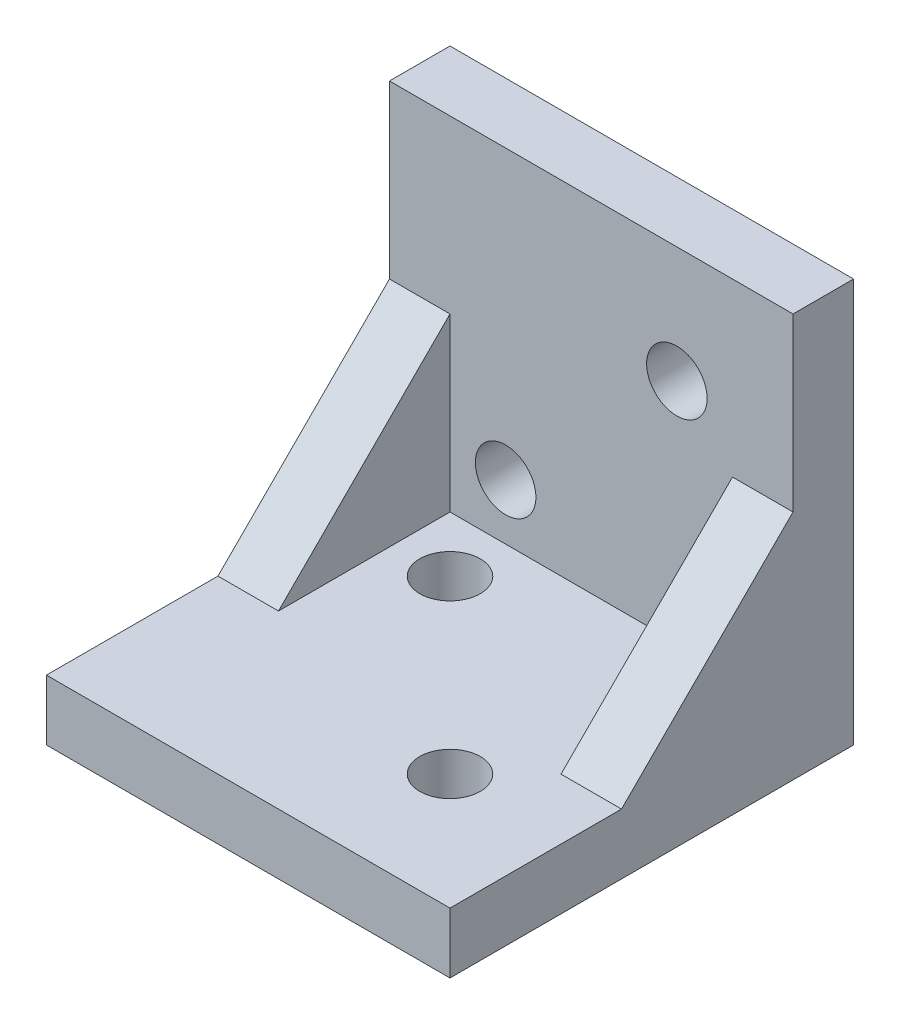
SolidWorks part; units mm, degrees
ref_plane "Front Plane" through (0, 0, 0) normal (0, 0, 1) x (1, 0, 0)
ref_plane "Top Plane" through (0, 0, 0) normal (0, 1, 0) x (1, 0, 0)
ref_plane "Right Plane" through (0, 0, 0) normal (1, 0, 0) x (0, 0, -1)
sketch "Sketch1" plane through (0, 0, 0) normal (0, 1, 0) x (1, 0, 0)
  line L0 (0, 0) -> (-10, 10) construction
  line L1 (-10, -10) -> (10, -10)
  line L2 (-10, -10) -> (-10, 10)
  line L3 (-10, 10) -> (10, 10)
  line L4 (10, -10) -> (10, 10)
  line L5 (-10, -10) -> (10, 10) construction
  line L7 (0, 0) -> (10, -10) construction
  circle A0 centre (-4.2426, 4.2426) radius 1.5
  circle A2 centre (4.2426, -4.2426) radius 1.5
  point P0 (0, 0)
  point P9 (-5, 5)
  point P10 (4.1299, -3.2213)
  point P12 (0, 0)
  point P13 (0, 0)
  point P14 (0, 0)
  point P15 (0, 0)
  point P16 (-23.6436, 6.8969)
  point P17 (-4.4087, 4.4087)
  dimension "D3" = 3
  dimension "D4" = 3
  dimension "D1" = 20
  dimension "D2" = 20
  dimension "D5" = 6
extrude "Boss-Extrude1" add sketch "Sketch1" along normal blind 3
sketch "Sketch2" plane through (0, 3, 0) normal (0, 1, 0) x (1, 0, 0)
  line L0 (10, -10) -> (10, 10) construction
  line L1 (-10, 10) -> (10, 10)
  line L2 (-10, 10) -> (-10, 7)
  line L3 (-10, 7) -> (10, 7)
  line L4 (10, 10) -> (10, 7)
  dimension "D1" = 3
extrude "Boss-Extrude2" add sketch "Sketch2" along normal blind 17
sketch "Sketch3" plane through (0, 0, -10) normal (0, 0, -1) x (-1, 0, 0)
  line L1 (-10, 20) -> (-10, 0) construction
  line L2 (10, 20) -> (10, 0) construction
  line L4 (-10, 20) -> (0, 10) construction
  line L5 (0, 11) -> (0, -11) construction
  line L6 (0, 10) -> (10, 0) construction
  line L7 (-10, 0) -> (10, 20) construction
  line L10 (11, 0) -> (-11, 0) construction
  circle A0 centre (-4.2426, 14.2426) radius 1.5
  circle A1 centre (4.2426, 5.7574) radius 1.5
  point P6 (-10, 0)
  point P13 (0, 0)
  point P19 (-0.8673, 14.6461)
  point P21 (10, 0)
  point P24 (-3.2833, 14.5842)
  point P25 (0, 0)
  dimension "D2" = 3
  dimension "D3" = 3
  dimension "D1" = 6
extrude "Cut-Extrude1" cut sketch "Sketch3" against normal blind 30
sketch "Sketch4" plane through (-10, 0, 0) normal (-1, 0, 0) x (0, 0, 1)
  line L0 (-7, 11.5) -> (1.5, 3)
  line L1 (-7, 20) -> (-7, 3) construction
  line L2 (-7, 3) -> (10, 3) construction
  line L3 (1.5, 3) -> (-7, 3)
  line L4 (-7, 3) -> (-7, 11.5)
extrude "Boss-Extrude3" add sketch "Sketch4" against normal blind 3
extrude "Boss-Extrude4" add sketch "Sketch4<2>" along normal blind 3 from surface starting at face at (10, 7.6667, -2.3333)
sketch "Sketch4<2>" plane through (-10, 0, 0) normal (-1, 0, 0) x (0, 0, 1) same geometry as "Sketch4"
